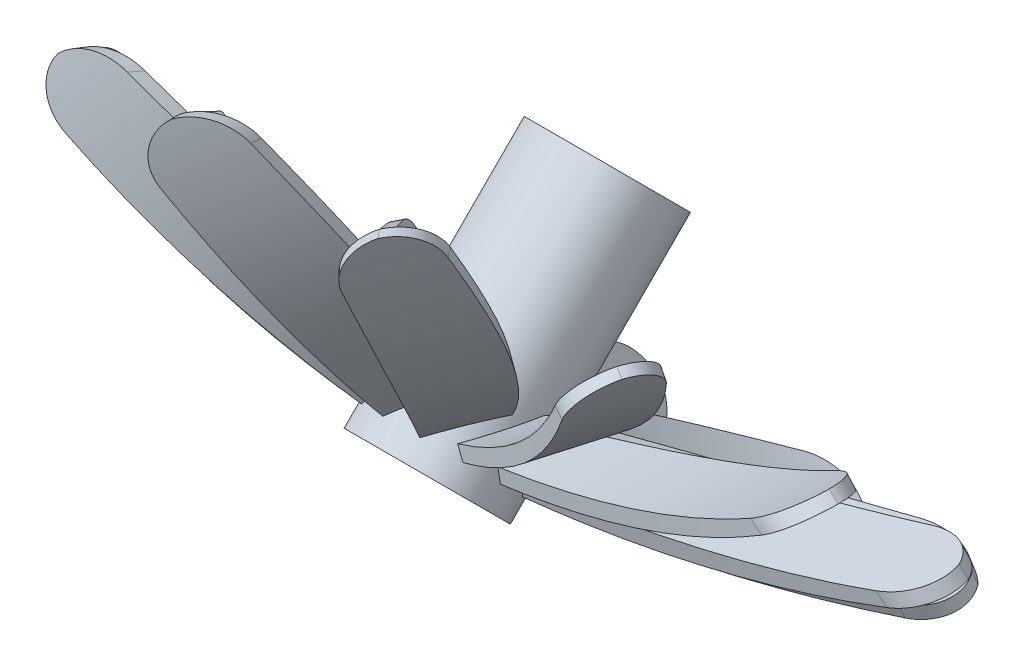
SolidWorks part; units mm, degrees
ref_plane "Front Plane" through (0, 0, 0) normal (0, 0, 1) x (1, 0, 0)
ref_plane "Top Plane" through (0, 0, 0) normal (0, 1, 0) x (1, 0, 0)
ref_plane "Right Plane" through (0, 0, 0) normal (1, 0, 0) x (0, 0, -1)
sketch "Sketch3" plane through (0, 0, 0) normal (0, 0, 1) x (1, 0, 0)
  line L0 (0, 0) -> (0, -3)
  line L1 (82.4519, 28.5168) -> (85, 26.9334)
  arc A0 (0, 0) -> (82.4519, 28.5168) centre (-7.2858, 154.5223) ccw
  arc A1 (0, -3) -> (85, 26.9334) centre (-2.7665, 140.507) ccw
  dimension "D1" = 3
  dimension "D2" = 3
  dimension "D3" = 85
extrude "Boss-Extrude3" add sketch "Sketch3" along normal blind 30 and the other way blind 30
sketch "Sketch4" plane through (0, 0, 0) normal (0, 1, 0) x (1, 0, 0)
  line L0 (0, 30) -> (0, -30) construction
  line L1 (0, 6.7324) -> (-8.8863, 31.5554)
  line L2 (-8.8863, 31.5554) -> (92.4208, 32.3798)
  line L3 (92.4208, 32.3798) -> (90.1308, 6.7324)
  line L4 (0, -6.824) -> (-6.7796, -33.2958)
  line L5 (-6.7796, -33.2958) -> (94.0695, -33.2958)
  line L6 (94.0695, -33.2958) -> (90.1308, -10.2132)
  arc A0 (0, 6.7324) -> (90.1308, 6.7324) centre (45.0654, -134.0075) cw
  arc A1 (0, -6.824) -> (90.1308, -10.2132) centre (27.412, -477.9983) cw
  point P8 (90.1308, 6.7324)
extrude "Cut-Extrude1" cut sketch "Sketch4" against normal blind 30 and the other way blind 30
fillet "Fillet1" radius 10 2 edges at (83.7261, 27.725, 9.399) (83.7275, 27.7242, -8.6244)
sketch "Sketch5" plane through (0, 0, 0) normal (0, 1, 0) x (1, 0, 0)
  circle A0 centre (-15.4934, 0) radius 4.6432
extrude "Boss-Extrude4" add sketch "Sketch5" along normal blind 30 separate body
ref_point "Point2"
ref_axis "Axis2" through (-15.4934, 0, 0) along (0, -1, 0)
ref_plane "Plane2" through (-15.4934, 0, 0) normal (1, 0, 0) x (0, 0, -1)
ref_plane "Plane3" through (-7.7467, 0, -7.7467) normal (0.7071, 0, 0.7071) x (0, -1, 0)
ref_axis "Axis3" through (-15.4934, 0, 0) along (1, 0, 0)
ref_plane "Plane4" through (0, 0, 0) normal (0, -0.7071, 0.7071) x (1, 0, 0)
sketch "Sketch6" plane through (0, 0, 0) normal (0, -0.7071, 0.7071) x (1, 0, 0)
  line L0 (-15.4934, 0) -> (53.151, 0) construction
  circle A0 centre (-3.8094, 0) radius 1
  dimension "D1" = 2
sketch "Sketch7" plane through (0, 0, 0) normal (0, -0.7071, 0.7071) x (1, 0, 0)
  line L1 (-30.1809, 29.4108) -> (-6.6625, 29.4108)
  line L2 (-30.1809, 29.4108) -> (-30.1809, -17.5338)
  line L3 (-30.1809, -17.5338) -> (-6.6625, -17.5338)
  line L4 (-6.6625, 29.4108) -> (-6.6625, -17.5338)
extrude "Cut-Extrude2" cut sketch "Sketch7" against normal blind 30 and the other way blind 30
extrude "Boss-Extrude5" add sketch "Sketch6" along normal blind 1 separate body
pattern_circular "CirPattern1" count 12 over 360 about axis through (-3.8094, -0.7071, 0.7071) along (0, -0.7071, 0.7071) of bodies 104
sketch "Sketch8" plane through (0, -0.7071, 0.7071) normal (0, -0.7071, 0.7071) x (1, 0, 0)
  circle A0 centre (-3.8094, 0) radius 16
  dimension "D1" = 32
extrude "Boss-Extrude6" add sketch "Sketch8" along normal blind 10 and the other way blind 50
